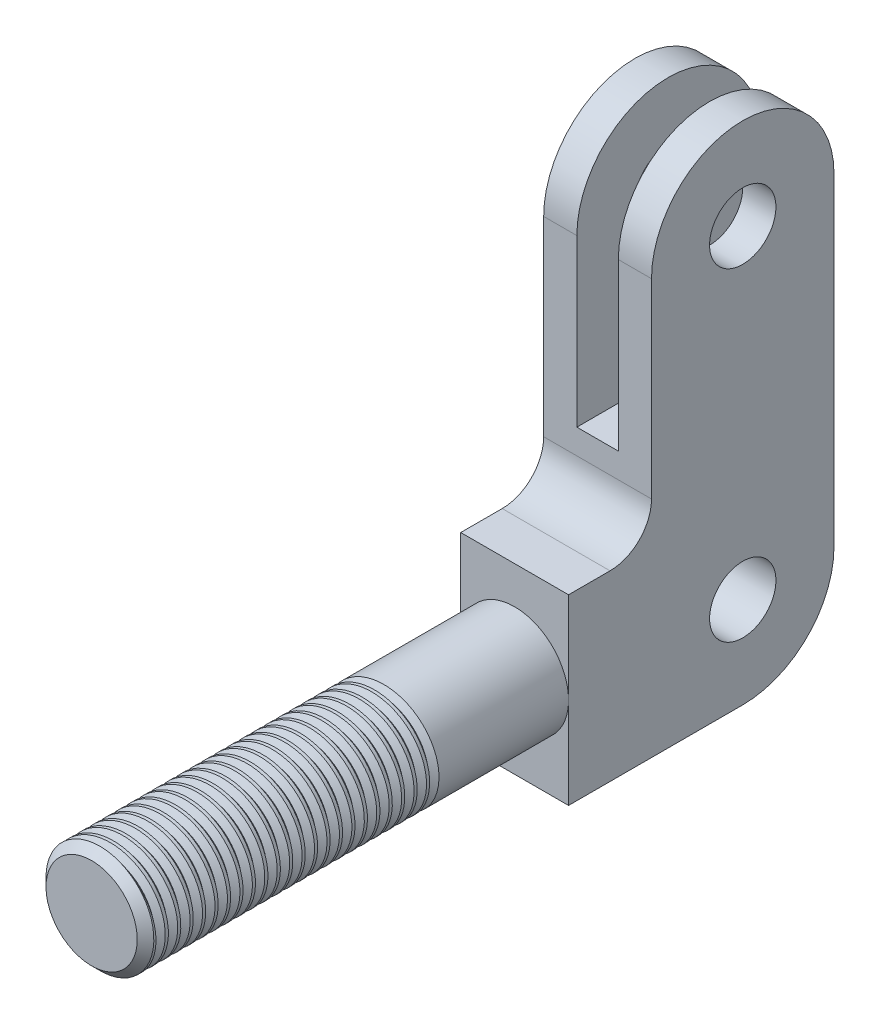
SolidWorks part; units mm, degrees
ref_plane "Front Plane" through (0, 0, 0) normal (0, 0, 1) x (1, 0, 0)
ref_plane "Top Plane" through (0, 0, 0) normal (0, 1, 0) x (1, 0, 0)
ref_plane "Right Plane" through (0, 0, 0) normal (1, 0, 0) x (0, 0, -1)
sketch "Sketch1" plane through (0, 0, 0) normal (1, 0, 0) x (0, 0, -1)
  line L0 (0, 0) -> (0, 32159.2384) construction
  line L1 (0, 0) -> (32159.2384, 0) construction
  line L2 (-21, 11) -> (-21, -11)
  line L3 (-21, -11) -> (0, -11)
  line L4 (11, 0) -> (11, 39)
  line L5 (-11, 39) -> (-11, 16)
  line L6 (-16, 11) -> (-21, 11)
  line L7 (-11, 19) -> (11, 19)
  arc A0 (0, -11) -> (11, 0) centre (0, 0) ccw
  arc A1 (11, 39) -> (-11, 39) centre (0, 39) ccw
  arc A2 (-11, 16) -> (-16, 11) centre (-16, 16) cw
  circle A3 centre (0, 39) radius 4
  circle A4 centre (0, 0) radius 4
  dimension "D1" = 22
  dimension "D3" = 11
  dimension "D5" = 11
  dimension "D6" = 5
  dimension "D7" = 8
  dimension "D8" = 8
  dimension "D2" = 50
  dimension "D4" = 32
  dimension "D9" = 30
extrude "Boss-Extrude1" add sketch "Sketch1" along normal mid plane 13 contours L5 A2 L6 L2 L3 A0 L4 L7 A4 region at (0, 3.6173, 4.7048)
extrude "Boss-Extrude2" add sketch "Sketch1<3>" along normal blind 4 from offset 2.5 contours L4 A1 L5 L7 A3 region at (0, 32.9416, 0)
sketch "Sketch1<3>" plane through (0, 0, 0) normal (1, 0, 0) x (0, 0, -1) same geometry as "Sketch1"
mirror "Mirror1" about plane through (0, 0, 0) normal (1, 0, 0) of "Boss-Extrude2"
sketch "Sketch2" plane through (0, 0, 21) normal (0, 0, 1) x (1, 0, 0)
  circle A0 centre (0, 0) radius 6.5
  dimension "D1" = 13
extrude "Boss-Extrude3" add sketch "Sketch2" along normal blind 50
thread "Thread1" pitch 1.5 method cut profile "Thread Profile1" start angle 0, offset 2, length 36, pitch 1.5, diameter 13
ref_plane "Plane1" through (-6.5, 0, 73) normal (0, 1, 0) x (1, 0, 0)
sketch "Thread Profile1" plane through (-6.5, 0, 73) normal (0, 1, 0) x (1, 0, 0)
  line L0 (0, 0) -> (0, 1.5) construction
  line L1 (0, 0) -> (0.8119, 0.4687)
  line L2 (0.8119, 0.4687) -> (0.8119, 0.6562)
  line L3 (0.8119, 0.6562) -> (0, 1.125)
  line L4 (0.8119, 0.5625) -> (0, 0.5625) construction
  line L11 (0, 0) -> (0, 1.125)
  point P2 (0, 0)
  dimension "Pitch" = 1.5
  dimension "Profile_Angle" = 60
  dimension "Profile_Land" = 0.1875
  dimension "Profile_Height" = 0.8119
sketch "Sketch7" plane through (0, 0, 71) normal (0, 0, 1) x (1, 0, 0)
  circle A0 centre (0, 0) radius 6.5
  point P2 (0, 0)
  dimension "D1" = 13
extrude "Boss-Extrude5" add sketch "Sketch7" along normal blind 1
chamfer "Chamfer2" distance 1 angle 45 1 edges at (6.5, 0, 72)
